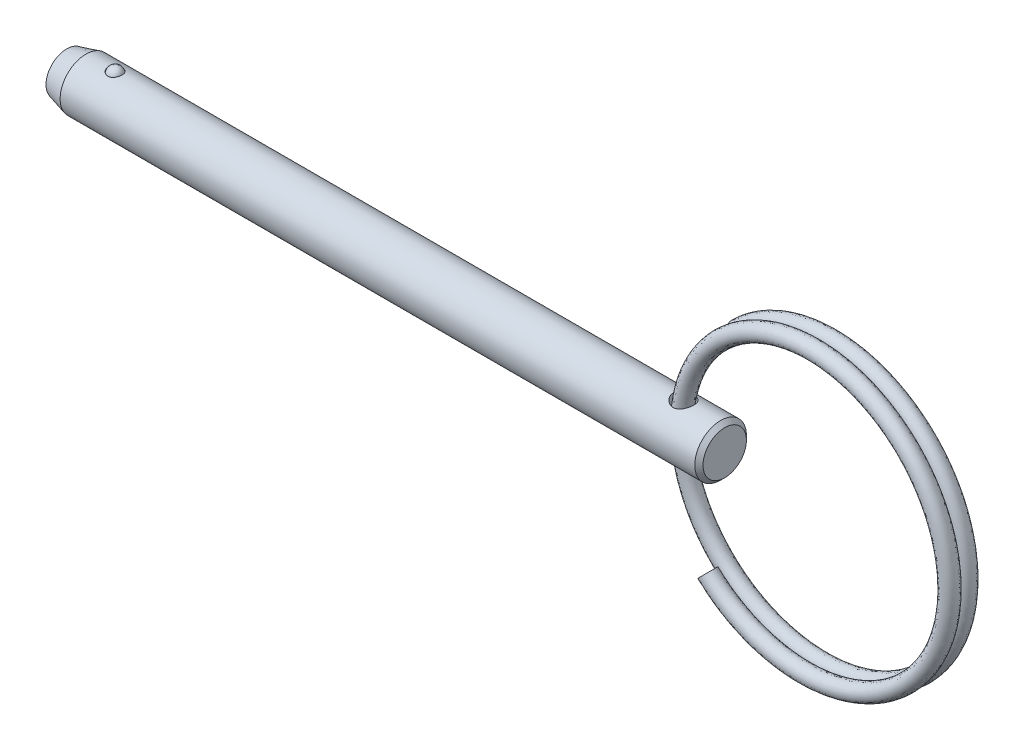
SolidWorks part; units mm, degrees
ref_plane "Front" through (0, 0, 0) normal (0, 0, 1) x (1, 0, 0)
ref_plane "Top" through (0, 0, 0) normal (0, 1, 0) x (1, 0, 0)
ref_plane "Right" through (0, 0, 0) normal (1, 0, 0) x (0, 0, -1)
sketch "Sketch1" plane through (0, 0, 0) normal (0, 0, 1) x (1, 0, 0)
  line L0 (30.3149, 2.0003) -> (29.9339, 2.3812)
  line L1 (29.9339, 2.3812) -> (30.3149, 2.3812) construction
  line L4 (30.3149, 2.0003) -> (30.3149, 0)
  line L5 (30.3149, 2.3812) -> (30.3149, 2.0003) construction
  line L16 (29.9339, 2.3812) -> (-28.5375, 2.3812)
  line L17 (-30.3149, 2.3812) -> (-30.3149, 1.905) construction
  line L19 (-28.5375, 2.3812) -> (-30.3149, 2.3812) construction
  line L22 (-30.3149, -2.3813) -> (-28.5375, -2.3812) construction
  line L23 (-25.8475, 2.1431) -> (-25.8475, -2.1431) construction
  line L24 (-30.3149, 0) -> (30.3149, 0)
  line L27 (30.3149, 0) -> (32.3152, 0) construction
  line L29 (-30.3149, 0) -> (-30.3149, -1.905) construction
  line L36 (25.5651, 0) -> (25.5651, 2.3812) construction
  line L37 (-30.3149, 1.905) -> (-30.3149, 0)
  line L38 (-28.5375, -2.3812) -> (30.3149, -2.3813) construction
  line L39 (-30.3149, -1.905) -> (-30.3149, -2.3813) construction
  line L40 (-28.5375, 2.3812) -> (-30.3149, 1.905)
  line L42 (-28.5375, -2.3812) -> (-30.3149, -1.905) construction
  line L43 (-28.5375, 2.3812) -> (-28.5375, -2.3812) construction
  circle A2 centre (-25.8475, 2.1431) radius 0.6572 construction
  point P35 (-25.2349, 2.3812)
  dimension "A1" = 15
revolve "Revolve1" add sketch "Sketch1" angle 360 about L27
sketch "Sketch2" plane through (0, 0, 0) normal (0, 0, 1) x (1, 0, 0)
  line L0 (-25.1648, 2.1431) -> (-26.5301, 2.1431)
  line L1 (-25.8475, 2.8004) -> (-25.8475, 2.8258) construction
  line L2 (-25.1648, 2.1431) -> (-23.7996, 2.1431) construction
  circle A0 centre (-25.8475, 2.1431) radius 0.6572 construction
  circle A1 centre (-25.8475, 2.1431) radius 0.6572 construction
  arc A2 (-26.5301, 2.1431) -> (-25.1648, 2.1431) centre (-25.8475, 2.1431) cw
  dimension "D1" = 0.0254
revolve "Cut-Revolve1" cut sketch "Sketch2" angle 360 about L2
sketch "Sketch3" plane through (0, 0, 0) normal (0, 0, 1) x (1, 0, 0)
  line L0 (-25.1902, 2.1431) -> (-26.5047, 2.1431)
  line L1 (-25.1902, 2.1431) -> (-23.8758, 2.1431) construction
  circle A0 centre (-25.8475, 2.1431) radius 0.6572 construction
  arc A1 (-25.1902, 2.1431) -> (-26.5047, 2.1431) centre (-25.8475, 2.1431) ccw
revolve "Revolve2" add sketch "Sketch3" angle 360 about L1
sketch "Sketch4" plane through (0, 0, 0) normal (0, 0, 1) x (1, 0, 0)
  line L1 (26.5176, -2.3812) -> (27.4701, -2.3812)
  line L2 (26.5176, -2.3812) -> (26.5176, 2.3812)
  line L3 (26.5176, 2.3812) -> (27.4701, 2.3812)
  line L4 (27.4701, -2.3812) -> (27.4701, 2.3812)
  line L5 (26.5176, -2.3812) -> (26.5176, -3.3337) construction
  line L6 (27.4701, 2.3812) -> (30.3149, 2.3812) construction
  line L8 (25.5651, -2.3812) -> (25.5651, 2.3812) construction
  line L9 (25.5651, 0) -> (26.5176, 0) construction
  line L11 (26.5176, 0) -> (27.4701, 0) construction
  line L12 (29.9339, 2.3812) -> (-28.5375, 2.3812) construction
  line L14 (-28.5375, -2.3812) -> (30.3149, -2.3812) construction
  dimension "D1" = 1.905
revolve "Cut-Revolve2" cut sketch "Sketch4" angle 360 about L2
sketch "Sketch5" plane through (0, 0, 0) normal (0, 0, 1) x (1, 0, 0)
  line L0 (0, 0) -> (25.6356, 0) construction
  line L1 (25.6356, 0) -> (25.6356, 2.3812) construction
  line L2 (29.9339, 2.3812) -> (-28.5375, 2.3812) construction
  line L3 (39.0976, 0) -> (52.5596, 0) construction
  line L4 (27.4701, 2.3812) -> (27.3996, 2.3812) construction
  line L5 (26.5176, 2.3812) -> (27.4701, 2.3812) construction
  line L6 (25.8479, 2.3812) -> (25.8479, -2.3812) construction
  line L7 (25.6356, 2.3812) -> (25.5651, 2.3812) construction
  line L8 (26.5176, -2.3812) -> (27.4701, -2.3812) construction
  line L9 (25.8479, -2.3812) -> (27.4701, -2.3812) construction
  line L10 (25.6356, 0) -> (39.0976, 0) construction
  line L12 (27.3996, 2.3812) -> (25.8479, 2.3812) construction
  line L13 (39.0976, 11.938) -> (39.0976, 13.462) construction
  circle A0 centre (39.0976, 0) radius 13.462
  circle A1 centre (39.0976, 0) radius 11.938 construction
  circle A2 centre (39.0976, 0) radius 12.7 construction
  point P26 (39.0976, 12.7)
curve "Helix/Spiral1" pitch 1.5494 height 1.3557 radius 13.462 left hand yes centre (39.0976, 0, 0) axis (0, 0, -1) start towards (1, 0, 0)
sketch "Sketch6" plane through (114.0038, 0, 0) normal (0, 1, 0) x (0, 0, -1)
  line L0 (0, 86.8442) -> (0, 87.6062) construction
  line L1 (0, 87.6062) -> (0, 88.3682) construction
  circle A0 centre (0, 87.6062) radius 0.762
  dimension "D1" = 1.524
sketch "Sketch7" plane through (0, 0, 0) normal (0, 0, 1) x (1, 0, 0)
  circle A0 centre (39.0976, 0) radius 13.462 construction
  circle A1 centre (39.0976, 0) radius 13.462
curve "Helix/Spiral2" pitch 1.5494 height 1.3557 radius 13.462 left hand yes centre (39.0976, 0, 0) axis (0, 0, 1) start towards (1, 0, 0)
sweep "Sweep1" add profiles "Sketch6" path "Helix/Spiral1"
sweep "Sweep2" add profiles "Sketch6<2>" path "Helix/Spiral2"
sketch "Sketch6<2>" plane through (114.0038, 0, 0) normal (0, 1, 0) x (0, 0, -1) same geometry as "Sketch6"
equation "\"D12@Sketch1\"=\"A@Sketch1\" * 0.80"
equation "\"D2@Sketch1\"=\"A@Sketch1\" * 0.9"
equation "\"D1@Sketch4\" = \"A@Sketch1\" / 2.5"
equation "\"Ring OD@Sketch5\" = \"R Ring Dia@Sketch5\" * 0.06"
equation "\"D4@Helix/Spiral1\"=\"Ring OD@Sketch5\" + 0.001"
equation "\"D1@Sketch6\"=\"Ring OD@Sketch5\""
equation "\"D4@Helix/Spiral2\" = \"D4@Helix/Spiral1\""
equation "\"D5@Helix/Spiral2\" = \"D5@Helix/Spiral1\""
